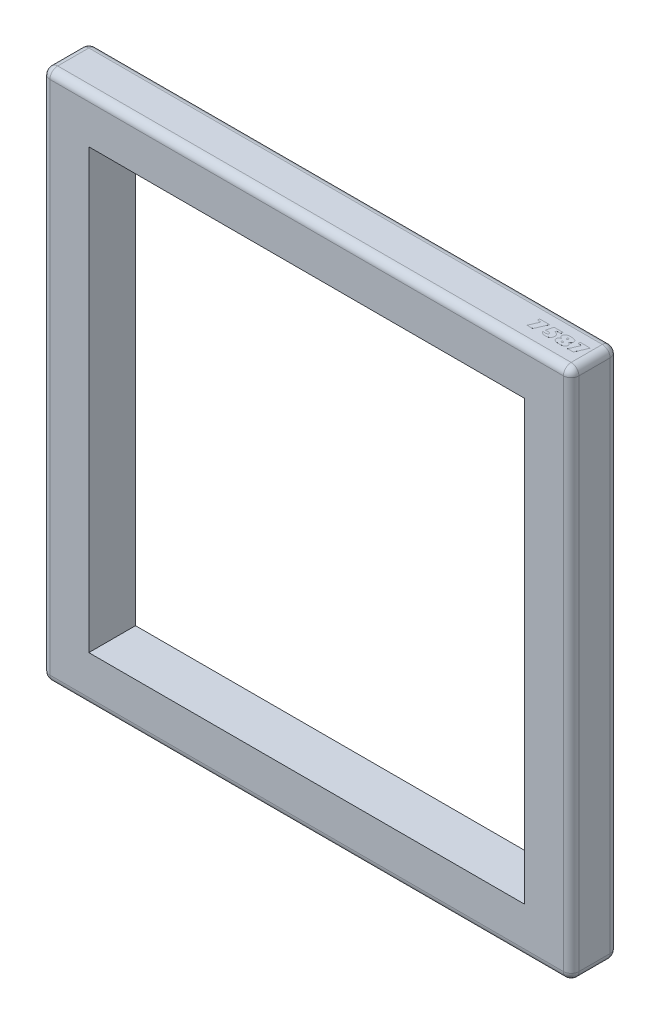
SolidWorks part; units mm, degrees
ref_plane "Front Plane" through (0, 0, 0) normal (0, 0, 1) x (1, 0, 0)
ref_plane "Top Plane" through (0, 0, 0) normal (0, 1, 0) x (1, 0, 0)
ref_plane "Right Plane" through (0, 0, 0) normal (1, 0, 0) x (0, 0, -1)
sketch "Sketch2" plane through (0, 0, 0) normal (0, 0, 1) x (1, 0, 0)
  line L0 (-38.1, 0) -> (-749.3, 0)
  line L1 (-749.3, 0) -> (-749.3, 715.137)
  line L2 (-749.3, 715.137) -> (-38.1, 715.137)
  line L3 (-38.1, 715.137) -> (-38.1, 0)
  line L5 (38.1, -76.2) -> (-825.5, -76.2)
  line L10 (38.1, -76.2) -> (38.1, 791.337)
  line L11 (38.1, 791.337) -> (-825.5, 791.337)
  line L12 (-825.5, -76.2) -> (-825.5, 791.337)
  dimension "D1" = 76.2
  dimension "D2" = 76.2
  dimension "D3" = 76.2
  dimension "D4" = 76.2
extrude "Boss-Extrude1" add sketch "Sketch2" against normal blind 76.2
fillet "Fillet1" radius 12.7 12 edges at (-825.5, 357.5685, 0) (-393.7, -76.2, -76.2) (38.1, -76.2, -38.1) (-393.7, -76.2, 0) (-825.5, -76.2, -38.1) (-825.5, 357.5685, -76.2) (38.1, 357.5685, -76.2) (-393.7, 791.337, -76.2) (38.1, 791.337, -38.1) (-825.5, 791.337, -38.1) (-393.7, 791.337, 0) (38.1, 357.5685, 0)
sketch "Sketch3" plane through (0, 791.337, 0) normal (0, 1, 0) x (1, 0, 0)
  text T0 "7587" font "Gill Sans Ultra Bold" height in points 72
extrude "Boss-Extrude2" add sketch "Sketch3" along normal blind 0.0254
